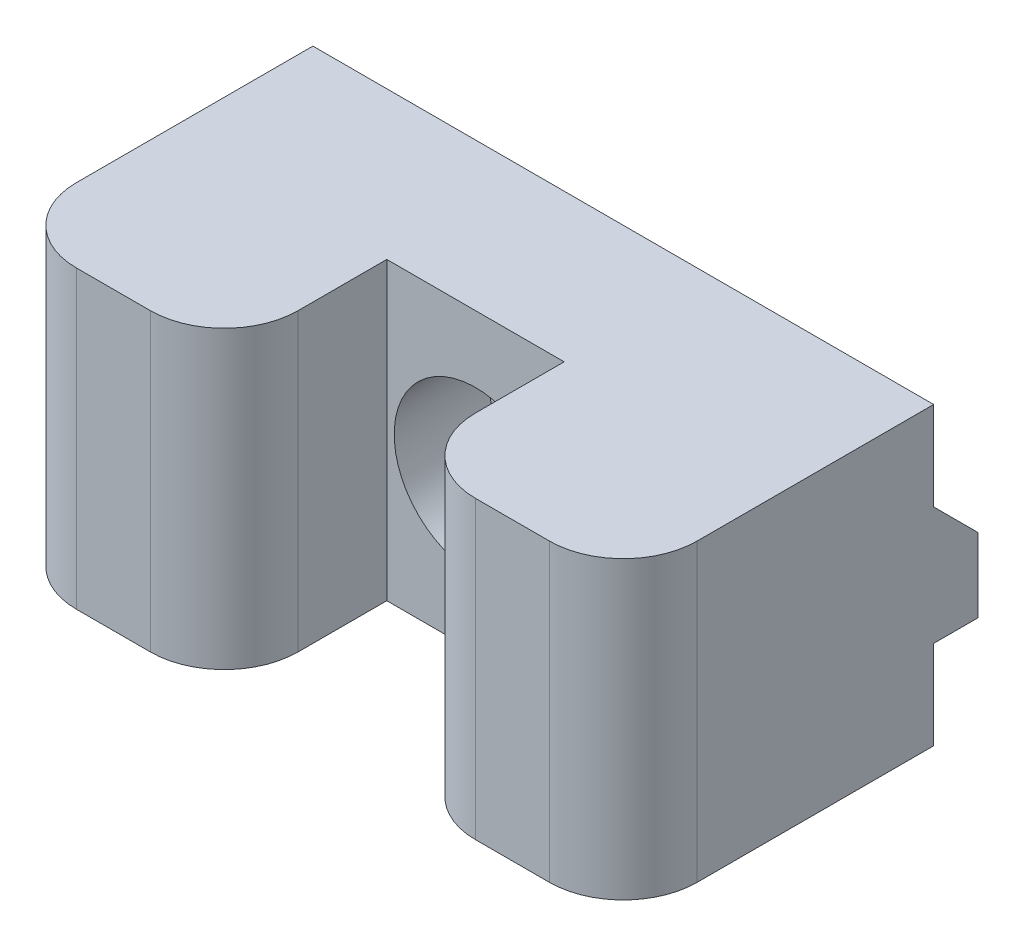
SolidWorks part; units mm, degrees
ref_plane "Přední rovina" through (0, 0, 0) normal (0, 0, 1) x (1, 0, 0)
ref_plane "Horní rovina" through (0, 0, 0) normal (0, 1, 0) x (1, 0, 0)
ref_plane "Pravá rovina" through (0, 0, 0) normal (1, 0, 0) x (0, 0, -1)
sketch "Base sketch" plane through (0, 0, 0) normal (0, 0, 1) x (1, 0, 0)
  line L1 (-21, 10) -> (21, 10)
  line L2 (-21, 10) -> (-21, -10)
  line L3 (-21, -10) -> (21, -10)
  line L4 (21, 10) -> (21, -10)
  line L5 (-21, 10) -> (21, -10) construction
  line L6 (-21, -10) -> (21, 10) construction
  point P0 (0, 0)
  dimension "D1" = 42
  dimension "D2" = 20
extrude "Base" add sketch "Base sketch" along normal blind 10
sketch "Magnet tower sketch" plane through (0, -10, 0) normal (0, -1, 0) x (1, 0, 0)
  line L0 (0, 0) -> (0, 10)
  line L1 (-21, 10) -> (21, 10) construction
  line L2 (21, 10) -> (6, 10)
  line L3 (-21, 10) -> (-6, 10)
  line L4 (-21, 10) -> (-21, 21)
  line L5 (-21, 21) -> (-6, 21)
  line L6 (-6, 10) -> (-6, 21)
  line L7 (21, 10) -> (21, 21)
  line L8 (6, 10) -> (6, 21)
  line L9 (21, 21) -> (6, 21)
  line M8 (21, 10) -> (-21, 10)
  dimension "D1" = 15
  dimension "D2" = 11
extrude "Magnet tower" add sketch "Magnet tower sketch" against normal up to surface (20 mm away) contours L6 L5 L4 M8 | L7 L9 L8 M8 region at (-13.5, -10, 15.5) region at (13.5, -10, 15.5) up to face at (0, 10, 5)
sketch "Magnet holes sketch" plane through (0, -10, 0) normal (0, -1, 0) x (1, 0, 0)
  line L0 (0, 0) -> (0, 10)
  line L1 (-6, 10) -> (6, 10) construction
  circle A0 centre (-13.5, 14) radius 5.5
  circle A1 centre (13.5, 14) radius 5.5
  point P5 (-13.5, 14)
  dimension "D3" = 11
  dimension "D1" = 13.5
  dimension "D2" = 14
extrude "Magnet holes" cut sketch "Magnet holes sketch" against normal blind 5 contours A0 | A1 region at (-13.5, -10, 14) region at (13.5, -10, 14)
sketch "Mount screw sketch" plane through (0, 0, 10) normal (0, 0, 1) x (1, 0, 0)
  line L0 (0, 10) -> (0, -10)
  line L1 (6, 10) -> (-6, 10) construction
  line L2 (-6, -10) -> (6, -10) construction
  point P6 (0, 0)
hole_wizard "Mount screw" positions "Skica5" profile "Skica6" counterbore size "M6" standard "ISO" end condition up to next
sketch "Skica5" plane through (0, 0, 10) normal (0, 0, 1) x (1, 0, 0)
  point P0 (0, 0)
sketch "Skica6" plane through (0, 0, 10) normal (1, 0, 0) x (0, -1, 0)
  line L0 (0, 0) -> (0, 10)
  line L1 (0, 10) -> (3.3, 10)
  line L3 (3.3, 10) -> (3.3, 6.4)
  line L4 (3.3, 6.4) -> (5.5, 6.4)
  line L5 (5.5, 6.4) -> (5.5, 0)
  line L7 (5.5, 0) -> (0, 0)
  line L11 (0, -6.35) -> (0, 107.95) construction
  dimension "Průměr díry skrz" = 6.6
  dimension "Hloubka díry skrz" = 10
  dimension "Průměr válcového zahloubení" = 11
  dimension "Hloubka válcového zahloubení" = 6.4
fillet "Rounding" radius 5 4 edges at (21, 0, 21) (6, 0, 21) (-6, 0, 21) (-21, 0, 21)
sketch "Profile clip sketch" plane through (0, 0, 0) normal (0, 0, -1) x (-1, 0, 0)
  line L0 (21, 10) -> (21, -10) construction
  line L1 (-21, 4) -> (21, 4)
  line L2 (-21, 4) -> (-21, -4)
  line L3 (-21, -4) -> (21, -4)
  line L4 (21, 4) -> (21, -4)
  line L5 (-21, 4) -> (21, -4) construction
  line L6 (-21, -4) -> (21, 4) construction
  circle A0 centre (0, 0) radius 9
  point P0 (0, 0)
  line M3 (-21, 10) -> (-21, -10)
  line M5 (21, -10) -> (21, 10)
  dimension "D2" = 18
  dimension "D1" = 8
extrude "Profile clip" add sketch "Profile clip sketch" along normal blind 3 contours A0 L1 L3 M3 | A0 L3 L1 M5 region at (14.844, 0, 0) region at (-14.844, 0, 0)
chamfer "Profile clip angle" distance 3 angle 45 2 edges at (-14.5311, 4, -3) (14.5311, 4, -3)
